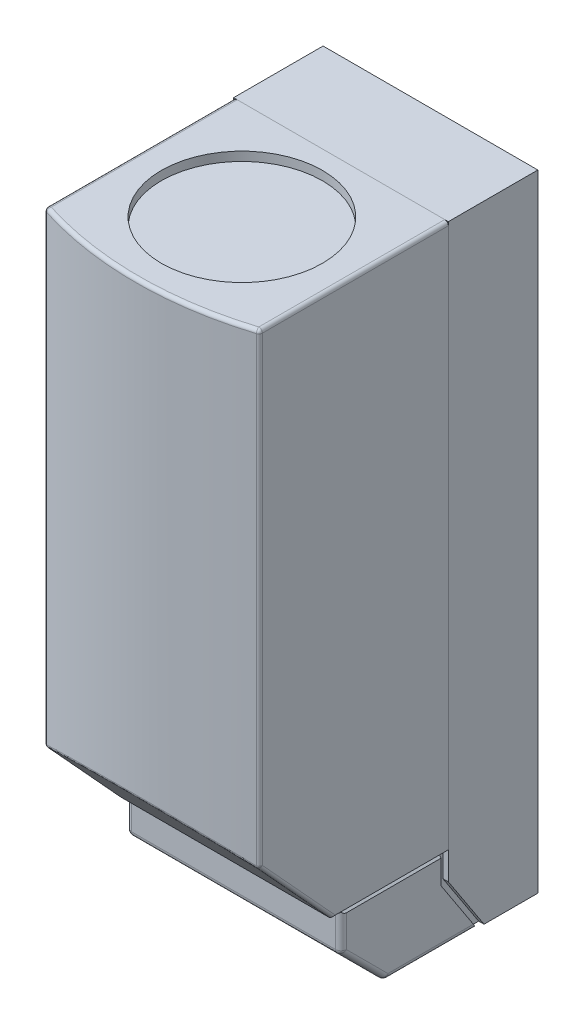
SolidWorks part; units mm, degrees
ref_plane "Ön Düzlem" through (0, 0, 0) normal (0, 0, 1) x (1, 0, 0)
ref_plane "Üst Düzlem" through (0, 0, 0) normal (0, 1, 0) x (1, 0, 0)
ref_plane "Sağ Düzlem" through (0, 0, 0) normal (1, 0, 0) x (0, 0, -1)
sketch "Çizim1" plane through (0, 0, 0) normal (0, 0, 1) x (1, 0, 0)
  line L1 (60, -175) -> (-60, -175)
  line L2 (60, -175) -> (60, 175)
  line L3 (60, 175) -> (-60, 175)
  line L4 (-60, -175) -> (-60, 175)
  line L5 (60, -175) -> (-60, 175) construction
  line L6 (60, 175) -> (-60, -175) construction
  point P0 (0, 0)
  dimension "D1" = 350
  dimension "D2" = 120
extrude "Yükseklik-Ekstrüzyon1" add sketch "Çizim1" along normal blind 50
sketch "Çizim2" plane through (0, 0, 50) normal (0, 0, 1) x (1, 0, 0)
  line L0 (60, -175) -> (60, 175) construction
  line L1 (-60, -175) -> (60, -175)
  line L2 (-60, -175) -> (-60, -130)
  line L3 (-60, -130) -> (60, -130)
  line L4 (60, -175) -> (60, -130)
  dimension "D1" = 45
extrude "Yükseklik-Ekstrüzyon2" add sketch "Çizim2" along normal blind 60
sketch "Çizim3" plane through (0, 0, 50) normal (0, 0, 1) x (1, 0, 0)
  line L4 (-60, -130) -> (60, -130)
  line L5 (60, -130) -> (60, 175)
  line L6 (60, 175) -> (-60, 175)
  line L7 (-60, 175) -> (-60, -130)
  line L8 (-60, -130) -> (60, -130)
  line L9 (60, -130) -> (60, 175)
  line L10 (60, 175) -> (-60, 175)
  line L11 (-60, 175) -> (-60, -130)
  dimension "D1" = 0
extrude "Yükseklik-Ekstrüzyon3" add sketch "Çizim3" along normal blind 120 separate body
chamfer "Pah1" distance 25 angle 45 1 edges at (0, -175, 110)
chamfer "Pah2" distance 55 distance2 60 1 edges at (0, -130, 170) first distance on face at (0, -130, 110)
sketch "Çizim4" plane through (0, 175, 0) normal (0, 1, 0) x (1, 0, 0)
  line L0 (-60, -170) -> (-60, -50) construction
  line L1 (60, -170) -> (60, -50) construction
  line L3 (-60, -155.3713) -> (-60, -181.1023)
  line L4 (-60, -181.1023) -> (60, -181.1023)
  line L5 (60, -181.1023) -> (60, -155.3713)
  arc A0 (-60, -155.3713) -> (60, -155.3713) centre (0, 29.5734) ccw
extrude "Kes-Ekstrüzyon1" cut sketch "Çizim4" against normal blind 313
sketch "Çizim5" plane through (-60, 0, 0) normal (-1, 0, 0) x (0, 0, 1)
  line L0 (50, -144.5116) -> (54, -144.5116)
  line L1 (50, -130) -> (54, -130)
  line L2 (50, -130) -> (50, -144.5116)
  line L3 (50, -144.5116) -> (54, -144.5116)
  line L4 (54, -130) -> (54, -144.5116)
  line L5 (50, -144.5116) -> (29.1388, -176.3995)
  line L6 (54, -144.5116) -> (33.1388, -176.3995)
  line L8 (29.1388, -176.3995) -> (33.1388, -176.3995)
  line M2 (0, -175) -> (85, -175)
  line M5 (110, -130) -> (50, -130)
  dimension "D1" = 4
extrude "Kes-Ekstrüzyon2" cut sketch "Çizim5" against normal blind 3 contours L6 L0 L5 M2 | L4 L2 L0 M5 region at (-60, -137.2558, 52) region at (-60, -159.7558, 42.0272)
chamfer "Pah3" distance 1 angle 45 2 edges at (0, -130, 110) (-60, -130, 82)
chamfer "Pah4" distance 1 angle 45 2 edges at (-60, -130, 82.5) (60, -130, 82.5)
chamfer "Pah5" distance 1 angle 45 1 edges at (60, -130, 79.5)
fillet "Radyus1" radius 2 8 edges at (-60, 175, 102.6856) (60, 175, 102.6856) (0, 175, 164.8605) (60, -107.4793, 135.644) (0, -75.6067, 164.8605) (-60, -107.4793, 135.644) (60, 44.5207, 155.3713) (-60, 44.5207, 155.3713)
fillet "Radyus2" radius 3 6 edges at (60, -162.5, 97.5) (60, -140.5, 110) (-60, -140.5, 110) (-60, -175, 59.5272) (-60, -162.5, 97.5) (0, -150, 110)
mirror "Aynalama1" about plane through (0, 0, 0) normal (1, 0, 0) of "Kes-Ekstrüzyon2"
fillet "Radyus3" radius 3 4 edges at (-59.1213, -174.1213, 84.636) (0, -175, 85) (59.1213, -175, 83.7574) (60, -175, 57.4059)
sketch "Çizim8" plane through (0, 175, 0) normal (0, 1, 0) x (1, 0, 0)
  line L0 (0, -45.8605) -> (0, -164.8605) construction
  arc A0 (-58.6028, -155.8188) -> (58.6028, -155.8188) centre (0, 29.5734) ccw construction
  circle A1 centre (0, -105.3605) radius 45
  dimension "D2" = 90
  dimension "D1" = 119
extrude "Kes-Ekstrüzyon3" cut sketch "Çizim8" against normal blind 5
